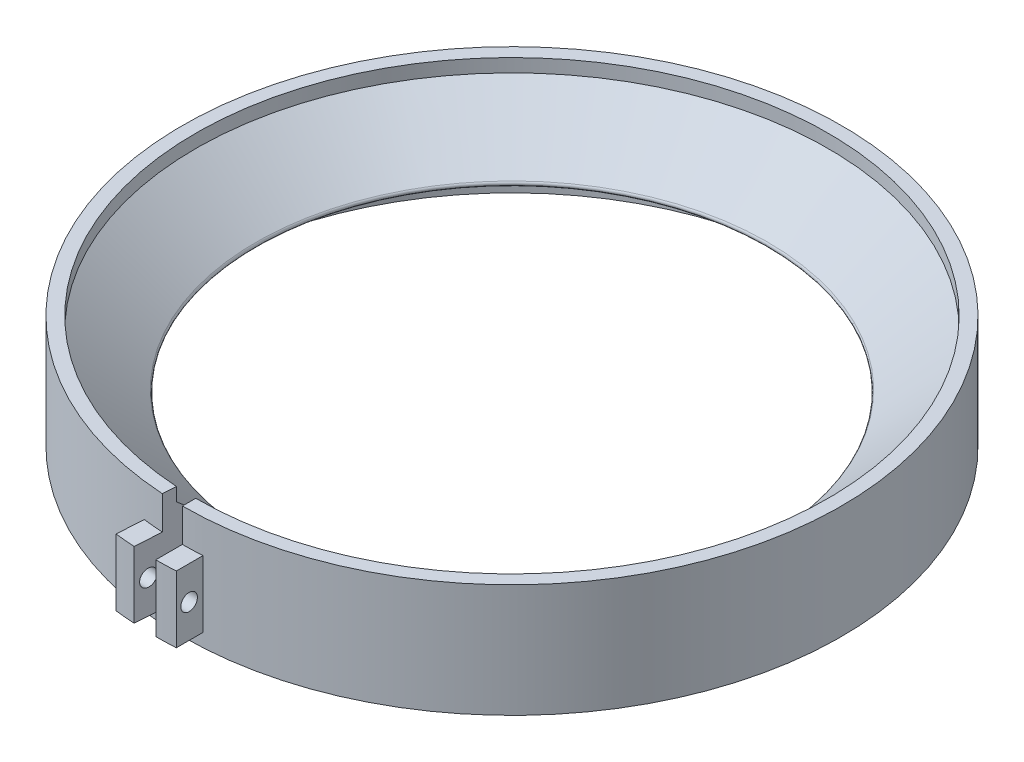
SolidWorks part; units mm, degrees
ref_plane "Front Plane" through (0, 0, 0) normal (0, 0, 1) x (1, 0, 0)
ref_plane "Top Plane" through (0, 0, 0) normal (0, 1, 0) x (1, 0, 0)
ref_plane "Right Plane" through (0, 0, 0) normal (1, 0, 0) x (0, 0, -1)
sketch "Sketch1" plane through (0, 0, 0) normal (0, 0, 1) x (1, 0, 0)
  line L0 (-42.6436, 0) -> (43.9692, 0) construction
  line L1 (0.6628, 0) -> (-8.8712, 8)
  line L2 (0.6628, 0) -> (-7.9975, -5)
  line L3 (1.4628, -0.6928) -> (-5.9975, -5) construction
  line L5 (-8.8712, 8) -> (-7.6267, 8) construction
  line L6 (-7.9975, -5) -> (-5.9975, -5) construction
  line L7 (38.6588, 8) -> (38.6588, -7.609) construction
  line L8 (2.3996, -0.152) -> (-16.3835, 15.6089) construction
  line L9 (0.6628, 0) -> (-17.0263, 14.8429) construction
  line L10 (0.6628, 0) -> (-17.9865, -10.7671) construction
  line L11 (2.3996, -0.152) -> (-17.4865, -11.6332) construction
  line L12 (0.6628, 0) -> (2.2628, 0) construction
  line L13 (1.4628, -0.6928) -> (1.4628, 0.373) construction
  line L14 (1.4628, 0.373) -> (-7.6267, 8) construction
  line L15 (-8.8712, 8) -> (38.6588, 8)
  line L16 (-7.9975, -5) -> (38.6588, -5)
  line L17 (38.6588, 8) -> (38.6588, -5)
  point P11 (1.4628, 0)
  dimension "D1" = 40
  dimension "D2" = 30
  dimension "D4" = 8
  dimension "D5" = 5
  dimension "D6" = 47.53
  dimension "D7" = 1.6
  dimension "D8" = 0.8
  dimension "D3" = 1
revolve "Revolve1" add sketch "Sketch1" angle 360 about L7
scale "Scale1" [suppressed]
fillet "Fillet2" radius 0.4 1 edges at (38.6588, 0, 37.996)
sketch "Sketch5" plane through (0, -5, 0) normal (0, -1, 0) x (1, 0, 0)
  circle A2 centre (38.6588, 0) radius 46.6562 construction
  circle A3 centre (38.6588, 0) radius 46.6562
extrude "Boss-Extrude4" add sketch "Sketch5" along normal blind 2
sketch "Sketch6" plane through (0, 8, 0) normal (0, 1, 0) x (1, 0, 0)
  circle A2 centre (38.6588, 0) radius 47.53 construction
  circle A3 centre (38.6588, 0) radius 47.53
extrude "Boss-Extrude5" add sketch "Sketch6" along normal blind 2
sketch "Sketch9" plane through (0, 0, 0) normal (0, 1, 0) x (1, 0, 0)
  circle A5 centre (38.6588, 0) radius 49.53
  circle A6 centre (38.6588, 0) radius 49.53
  dimension "D1" = 2
extrude "Boss-Extrude6" add sketch "Sketch9" along normal up to surface and the other way up to surface separate body up to face at (38.6588, 10, 47.53) other way up to face at (38.6588, -7, -46.6562)
sketch "Sketch7" plane through (0, 0, 0) normal (0, 0, 1) x (1, 0, 0)
  line L0 (-42.6436, 0) -> (43.9692, 0) construction
  line L1 (0.6628, 0) -> (-8.8712, 8)
  line L2 (0.6628, 0) -> (-7.9975, -5)
  line L3 (1.4628, -0.6928) -> (-5.9975, -5) construction
  line L5 (-8.8712, 8) -> (-7.6267, 8) construction
  line L6 (-7.9975, -5) -> (-5.9975, -5) construction
  line L7 (38.6588, 8) -> (38.6588, -7.609) construction
  line L8 (2.3996, -0.152) -> (-16.3835, 15.6089) construction
  line L9 (0.6628, 0) -> (-17.0263, 14.8429) construction
  line L10 (0.6628, 0) -> (-17.9865, -10.7671) construction
  line L11 (2.3996, -0.152) -> (-17.4865, -11.6332) construction
  line L12 (0.6628, 0) -> (2.2628, 0) construction
  line L13 (1.4628, -0.6928) -> (1.4628, 0.373) construction
  line L14 (1.4628, 0.373) -> (-7.6267, 8) construction
  line L15 (-8.8712, 8) -> (38.6588, 8)
  line L16 (-7.9975, -5) -> (38.6588, -5)
  line L17 (38.6588, 8) -> (38.6588, -5)
  point P11 (1.4628, 0)
  dimension "D1" = 40
  dimension "D2" = 30
  dimension "D4" = 8
  dimension "D5" = 5
  dimension "D6" = 47.53
  dimension "D7" = 1.6
  dimension "D8" = 0.8
  dimension "D3" = 1
revolve "Revolve2" add sketch "Sketch7" angle 3.6 about L17 reverse direction yes
combine bodies "Combine2" operation type subtract main body 116 bodies to subtract 115 114
sketch "Sketch12" plane through (0, 0, 0) normal (0, 1, 0) x (1, 0, 0)
  line L0 (38.6588, 49.53) -> (38.6588, -49.53) construction
  line L1 (38.6588, 0) -> (38.6588, -55.3083)
  line L2 (38.6588, 0) -> (35.1105, -56.3973)
  line L3 (35.1105, -56.3973) -> (38.6588, -55.3083)
  circle A0 centre (38.6588, 0) radius 49.53 construction
  dimension "D1" = 3.6
extrude "Cut-Extrude1" cut sketch "Sketch12" against normal through all and the other way through all
sketch "Sketch14" plane through (0, 0, 0) normal (0, 1, 0) x (1, 0, 0)
  line L4 (35.5487, -49.4323) -> (35.2976, -53.4244)
  line L5 (38.6588, -49.53) -> (38.6588, -53.53)
  line L6 (38.6588, -53.53) -> (38.6588, -49.53)
  line L7 (32.3088, -53.152) -> (32.5604, -49.1531)
  line L8 (41.6588, -53.4459) -> (41.6588, -49.4391)
  arc A0 (38.6588, -49.53) -> (35.5487, -49.4323) centre (38.6588, 0) ccw construction
  arc A1 (38.6588, -49.53) -> (41.6588, -49.4391) centre (38.6588, 0) ccw
  arc A2 (32.5604, -49.1531) -> (35.5487, -49.4323) centre (38.6588, 0) ccw
  arc A3 (38.6588, -53.53) -> (35.2976, -53.4244) centre (38.6588, 0) ccw
  arc A4 (38.6588, -53.53) -> (41.6588, -53.4459) centre (38.6588, 0) ccw
  arc A5 (32.3088, -53.152) -> (35.2976, -53.4244) centre (38.6588, 0) ccw
  point P9 (41.6588, -51.4425)
  dimension "D2" = 3
  dimension "D3" = 3
  dimension "D1" = 4
extrude "Boss-Extrude7" add sketch "Sketch14" along normal mid plane 10 contours L5 A4 L8 A1 | L7 A2 L4 A5 region at (40.1592, 0, 51.5008)
sketch "Sketch15" plane through (41.6588, 0, 0) normal (1, 0, 0) x (0, 0, -1)
  line L1 (-53.4459, 5) -> (-49.4391, 5) construction
  circle A0 centre (-51.5232, 0) radius 1.25
  dimension "D1" = 2.5
extrude "Cut-Extrude2" cut sketch "Sketch15" against normal up to next
sketch "Sketch16" plane through (35.5123, 0, 2.2342) normal (-0.998, 0, -0.0628) x (-0.0628, 0, 0.998)
  line L0 (54.483, 0) -> (-54.483, 0) construction
  circle A0 centre (49.0725, 0) radius 1.25
  dimension "D1" = 2.5
extrude "Cut-Extrude3" cut sketch "Sketch16" against normal up to next
